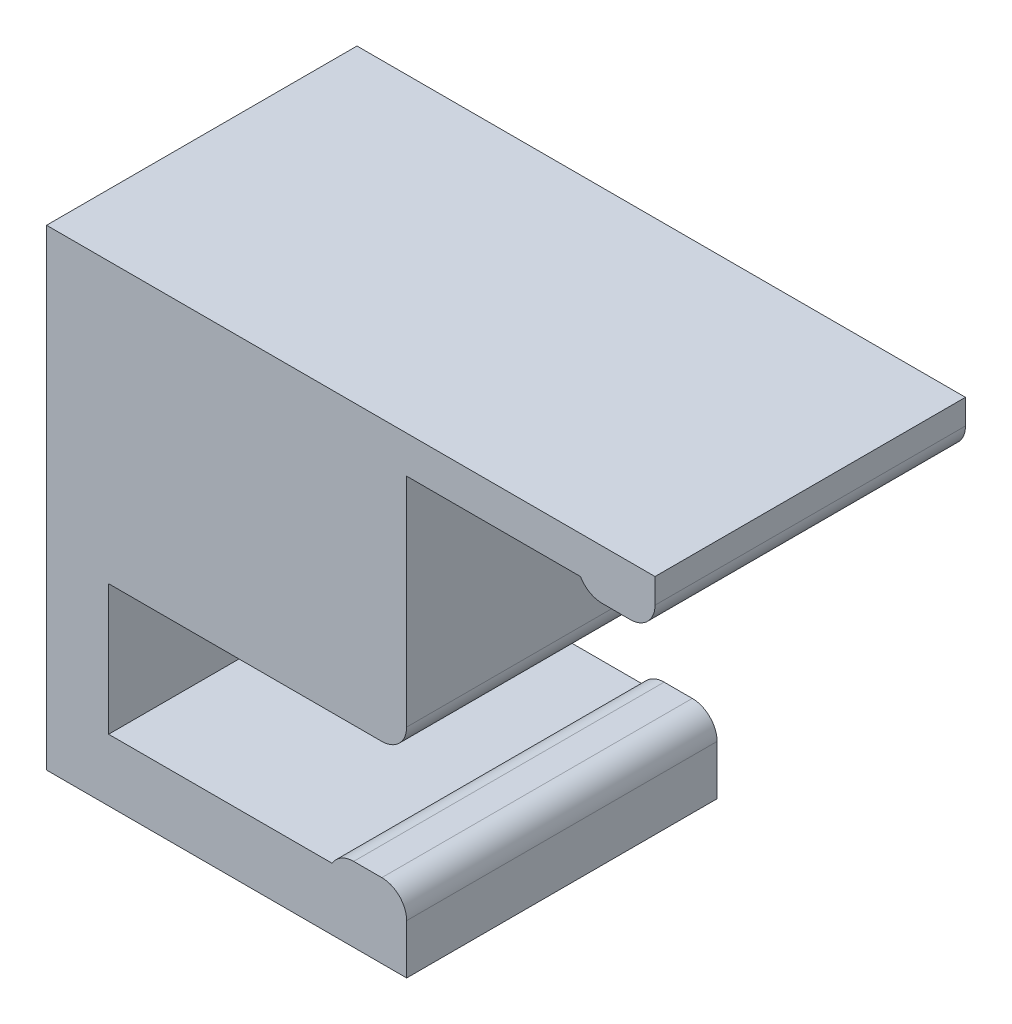
SolidWorks part; units mm, degrees
material "ABS"
ref_plane "Front Plane" through (0, 0, 0) normal (0, 0, 1) x (1, 0, 0)
ref_plane "Top Plane" through (0, 0, 0) normal (0, 1, 0) x (1, 0, 0)
ref_plane "Right Plane" through (0, 0, 0) normal (1, 0, 0) x (0, 0, -1)
sketch "Sketch1" plane through (0, 0, 0) normal (0, 0, 1) x (1, 0, 0)
  line L0 (0, 0) -> (14.5, 0)
  line L1 (0, 0) -> (0, 10.25) construction
  line L2 (0, 5.125) -> (14.5, 5.125) construction
  line L3 (2.5, 2.5) -> (2.5, 7.75)
  line L4 (24.5, 19) -> (0, 19)
  line L5 (0, 19) -> (0, 0)
  line L6 (2.5, 2.5) -> (14.5, 2.5)
  line L7 (14.5, 2.5) -> (14.5, 0)
  line L8 (14.5, 2.5) -> (14.5, 3)
  line L9 (14.5, 3) -> (11.5, 3)
  line L10 (11.5, 3) -> (11.5, 2.5)
  line L11 (14.5, 17.5) -> (24.5, 17.5)
  line L12 (14.5, 7.75) -> (14.5, 10.25) construction
  line L13 (2.5, 7.75) -> (14.5, 7.75)
  line L14 (0, 10.25) -> (14.5, 10.25) construction
  line L15 (2.5, 2.5) -> (0, 2.5) construction
  line L16 (2.5, 2.5) -> (2.5, 0) construction
  line L17 (24.5, 17.5) -> (24.5, 19)
  line L18 (14.5, 17.5) -> (14.5, 7.75)
  line L19 (24.5, 17.5) -> (24.5, 17)
  line L20 (24.5, 17) -> (21.5, 17)
  line L21 (21.5, 17) -> (21.5, 17.5)
  point P17 (2.5, 5.125)
  dimension "D1" = 2.5
  dimension "D2" = 0.5
  dimension "D3" = 3
  dimension "D4" = 12
  dimension "D5" = 5.25
  dimension "D6" = 1.5
  dimension "D7" = 10
  dimension "D8" = 9.75
  dimension "D9" = 3
  dimension "D10" = 0.5
extrude "Boss-Extrude1" add sketch "Sketch1" along normal blind 12.5 contours L18 L11 L17 L4 L5 L0 L7 L6 L3 L13 | L21 L20 L19 L11 | L9 L10 L6 L8 region at (7.7115, 11.2885, 0) region at (13, 2.75, 0) region at (23, 17.25, 0)
fillet "Fillet1" radius 1 5 edges at (24.5, 17, 6.25) (21.5, 17, 6.25) (11.5, 3, 6.25) (14.5, 3, 6.25) (14.5, 7.75, 6.25)
equation "\"D5@Sketch1\"=4.75+0.5"
